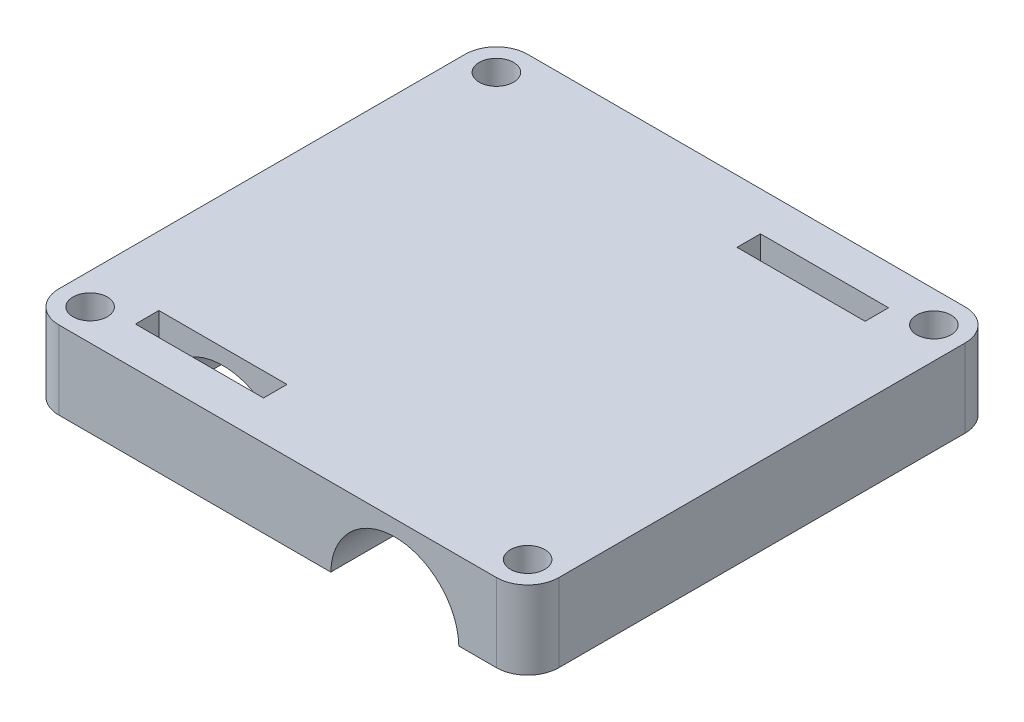
SolidWorks part; units mm, degrees
ref_plane "Front Plane" through (0, 0, 0) normal (0, 0, 1) x (1, 0, 0)
ref_plane "Top Plane" through (0, 0, 0) normal (0, 1, 0) x (1, 0, 0)
ref_plane "Right Plane" through (0, 0, 0) normal (1, 0, 0) x (0, 0, -1)
sketch "Sketch4" plane through (0, 0, 0) normal (0, 1, 0) x (1, 0, 0)
  line L1 (-16.8464, 7.0648) -> (15.1536, 7.0648)
  line L2 (-16.8464, 7.0648) -> (-16.8464, -22.9352)
  line L3 (-16.8464, -22.9352) -> (15.1536, -22.9352)
  line L4 (15.1536, 7.0648) -> (15.1536, -22.9352)
  dimension "D1" = 32
  dimension "D2" = 30
extrude "Boss-Extrude2" add sketch "Sketch4" along normal blind 5
fillet "Fillet3" radius 2 4 edges at (15.1536, 2.5, -7.0648) (-16.8464, 2.5, -7.0648) (-16.8464, 2.5, 22.9352) (15.1536, 2.5, 22.9352)
sketch "Sketch11" plane through (0, 0, -7.0648) normal (0, 0, -1) x (-1, 0, 0)
  line L0 (-13.1536, 0) -> (14.8464, 0) construction
  line L1 (16.8464, 5) -> (16.8464, 0) construction
  circle A0 centre (8.3464, -0.1) radius 4.1
  dimension "D1" = 8.2
  dimension "D2" = 0.1
  dimension "D3" = 8.5
sketch "Sketch12" plane through (0, 0, 22.9352) normal (0, 0, 1) x (1, 0, 0)
  line L0 (-14.8464, 0) -> (13.1536, 0) construction
  line L1 (15.1536, 5) -> (15.1536, 0) construction
  circle A0 centre (6.6536, -0.1) radius 4.1
  dimension "D1" = 8.2
  dimension "D2" = 0.1
  dimension "D3" = 8.5
extrude "Cut-Extrude6" cut sketch "Sketch11" against normal blind 26
extrude "Cut-Extrude7" cut sketch "Sketch12" against normal blind 26
sketch "Sketch13" plane through (0, 0, 0) normal (0, -1, 0) x (1, 0, 0)
  circle A0 centre (13.1536, -5.0648) radius 1.1
  circle A1 centre (-14.8464, -5.0648) radius 1.1
  circle A2 centre (-14.8464, 20.9352) radius 1.1
  circle A3 centre (13.1536, 20.9352) radius 1.1
  dimension "D1" = 2.2
  dimension "D2" = 2.2
  dimension "D3" = 2.2
  dimension "D4" = 2.2
extrude "Cut-Extrude8" cut sketch "Sketch13" against normal blind 5
sketch "Sketch14" plane through (0, 0, 0) normal (0, -1, 0) x (1, 0, 0)
  line L1 (-12.4452, 18.9352) -> (-4.2476, 18.9352)
  line L2 (-12.4452, 18.9352) -> (-12.4452, 20.4352)
  line L3 (-12.4452, 20.4352) -> (-4.2476, 20.4352)
  line L4 (-4.2476, 18.9352) -> (-4.2476, 20.4352)
  line L5 (2.5548, -3.0648) -> (10.7524, -3.0648)
  line L6 (2.5548, -3.0648) -> (2.5548, -4.5648)
  line L7 (2.5548, -4.5648) -> (10.7524, -4.5648)
  line L8 (10.7524, -3.0648) -> (10.7524, -4.5648)
  point P10 (-4.2476, 18.9352)
  point P12 (10.7524, -3.0648)
  dimension "D1" = 1.5
  dimension "D2" = 1.5
extrude "Cut-Extrude9" cut sketch "Sketch14" against normal blind 5
